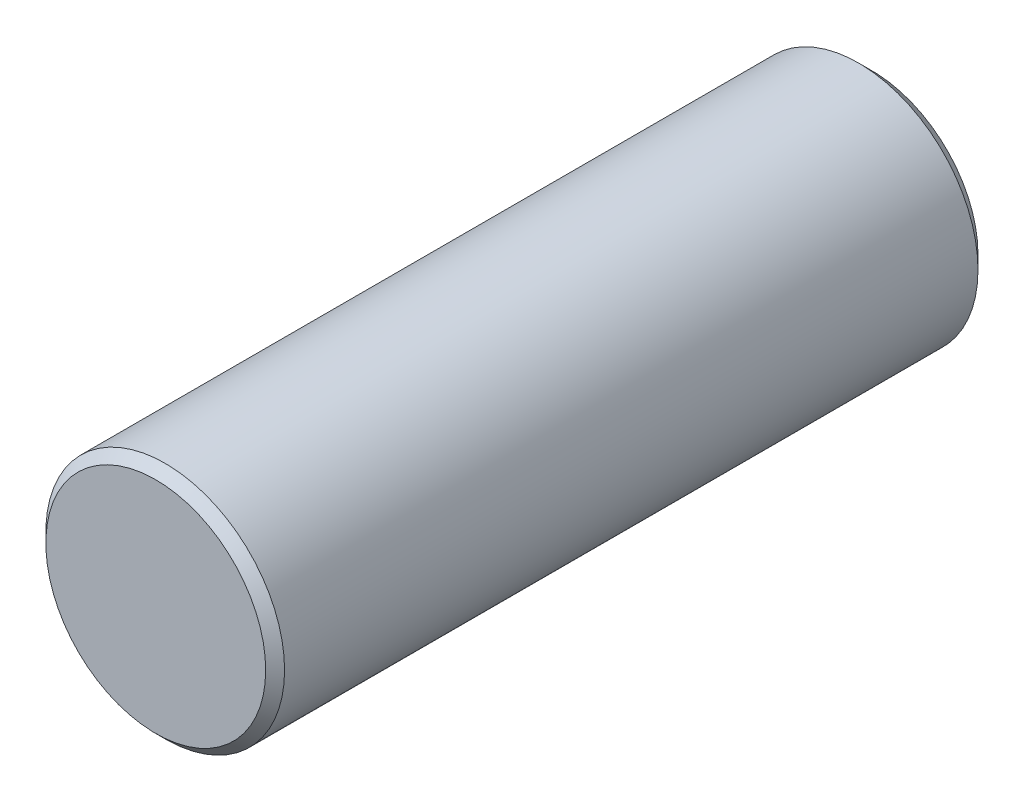
SolidWorks part; units mm, degrees
material "AISI 1045 Steel, cold drawn"
ref_plane "Front Plane" through (0, 0, 0) normal (0, 0, 1) x (1, 0, 0)
ref_plane "Top Plane" through (0, 0, 0) normal (0, 1, 0) x (1, 0, 0)
ref_plane "Right Plane" through (0, 0, 0) normal (1, 0, 0) x (0, 0, -1)
sketch "Sketch1" plane through (0, 0, 0) normal (1, 0, 0) x (0, 0, -1)
  line L0 (-9.525, 0) -> (-9.525, 2.9236)
  line L1 (-9.525, 2.9236) -> (-9.2736, 3.175)
  line L2 (-9.2736, 3.175) -> (9.1694, 3.175)
  line L3 (9.1694, 3.175) -> (9.525, 2.8194)
  line L4 (9.525, 2.8194) -> (9.525, 0)
  line L5 (9.525, 0) -> (-9.525, 0)
  line L6 (9.525, 0) -> (-9.525, 0) construction
revolve "Revolve1" add sketch "Sketch1" angle 360 about L6 reverse direction yes
ref_plane "dia1 XY" through (0, 0, 0) normal (0, 0, 1) x (1, 0, 0)
ref_plane "dia1 XZ" through (0, 0, 0) normal (0, -1, 0) x (-1, 0, 0)
ref_plane "dia1 YZ" through (-3.175, 0, 0) normal (1, 0, 0) x (0, 0, -1)
ref_axis "dia1 X" through (-80.9, 0, 0) along (1, 0, 0)
ref_axis "dia1 Y" through (-3.175, -50, 0) along (0, 1, 0)
ref_axis "dia1 Z" through (-3.175, 0, 80.9) along (0, 0, -1)
sketch3d "dia1"
  point P0 (-3.175, 0, 0)
ref_plane "dia2 XY" through (0, 0, 0) normal (0, 0, 1) x (1, 0, 0)
ref_plane "dia2 XZ" through (0, 0, 0) normal (0, -1, 0) x (-1, 0, 0)
ref_plane "dia2 YZ" through (3.175, 0, 0) normal (1, 0, 0) x (0, 0, -1)
ref_axis "dia2 X" through (-80.9, 0, 0) along (1, 0, 0)
ref_axis "dia2 Y" through (3.175, -50, 0) along (0, 1, 0)
ref_axis "dia2 Z" through (3.175, 0, 80.9) along (0, 0, -1)
sketch3d "dia2"
  point P0 (3.175, 0, 0)
ref_plane "pin XY" through (0, 0, 0) normal (0, 0, 1) x (1, 0, 0)
ref_plane "pin XZ" through (0, 0, 0) normal (0, -1, 0) x (-1, 0, 0)
ref_plane "pin YZ" through (0, 0, 0) normal (1, 0, 0) x (0, 0, -1)
ref_axis "pin X" through (-80.9, 0, 0) along (1, 0, 0)
ref_axis "pin Y" through (0, -50, 0) along (0, 1, 0)
ref_axis "pin Z" through (0, 0, 80.9) along (0, 0, -1)
sketch3d "pin"
  point P0 (0, 0, 0)
ref_plane "pin1 XY" through (0, 0, 0) normal (1, 0, 0) x (0, 0, -1)
ref_plane "pin1 XZ" through (0, 0, 0) normal (0, -1, 0) x (-1, 0, 0)
ref_plane "pin1 YZ" through (0, 0, 9.525) normal (0, 0, -1) x (-1, 0, 0)
ref_axis "pin1 X" through (0, 0, 80.9) along (0, 0, -1)
ref_axis "pin1 Y" through (0, -50, 9.525) along (0, 1, 0)
ref_axis "pin1 Z" through (80.9, 0, 9.525) along (-1, 0, 0)
sketch3d "pin1"
  point P0 (0, 0, 9.525)
ref_plane "pin2 XY" through (0, 0, 0) normal (1, 0, 0) x (0, 0, -1)
ref_plane "pin2 XZ" through (0, 0, 0) normal (0, -1, 0) x (-1, 0, 0)
ref_plane "pin2 YZ" through (0, 0, -9.525) normal (0, 0, -1) x (-1, 0, 0)
ref_axis "pin2 X" through (0, 0, 80.9) along (0, 0, -1)
ref_axis "pin2 Y" through (0, -50, -9.525) along (0, 1, 0)
ref_axis "pin2 Z" through (80.9, 0, -9.525) along (-1, 0, 0)
sketch3d "pin2"
  point P0 (0, 0, -9.525)
